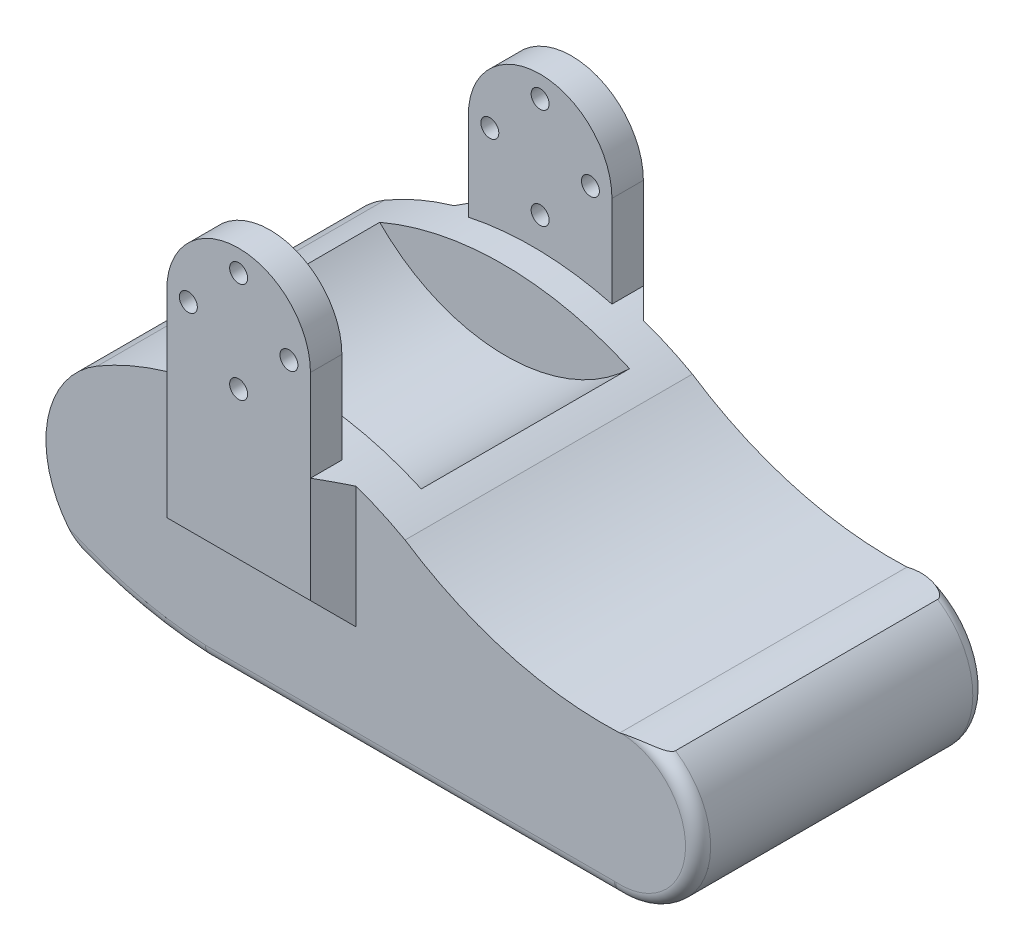
SolidWorks part; units mm, degrees
material "PLA"
ref_plane "Front Plane" through (0, 0, 0) normal (0, 0, 1) x (1, 0, 0)
ref_plane "Top Plane" through (0, 0, 0) normal (0, 1, 0) x (1, 0, 0)
ref_plane "Right Plane" through (0, 0, 0) normal (1, 0, 0) x (0, 0, -1)
sketch "Sketch1" plane through (0, 0, 0) normal (0, 0, 1) x (1, 0, 0)
  line L0 (-30, 0) -> (50, 0)
  line L1 (0, 0) -> (0, 25) construction
  line L2 (-30, 0) -> (-30, 25) construction
  line L3 (50, 0) -> (34.8329, 0) construction
  line L4 (-15, -2.8863) -> (48.734, -2.8863) construction
  line L5 (48.734, -2.8863) -> (48.734, 17.1137) construction
  line L6 (-15, -2.8863) -> (42.0254, -2.8863)
  line L7 (48.734, 17.1137) -> (42.7081, 17.1137) construction
  line L8 (-37.1668, 12.5) -> (-7.1668, 12.5) construction
  line L9 (-7.1668, 12.5) -> (12.8332, 12.5) construction
  line L10 (12.8332, 12.5) -> (12.8332, 25.4411) construction
  arc A0 (-30, 25) -> (-30, 0) centre (-22.6825, 12.5) ccw
  arc A7 (-30, 0) -> (-15, -2.8863) centre (-12.2067, 52.0503) ccw
  arc A8 (42.0254, -2.8863) -> (48.734, 17.1137) centre (42.7081, 8.0098) ccw
  arc A9 (48.734, 17.1137) -> (42.7081, 17.1137) centre (45.721, 5.4648) ccw
  arc A11 (-30, 25) -> (12.8332, 25.4411) centre (-8.1976, -12.2437) cw
  arc A12 (12.8332, 25.4411) -> (42.7081, 17.1137) centre (40.6286, 67.4056) ccw
  dimension "D5" = 20
  dimension "D6" = 30
  dimension "D1" = 30
  dimension "D2" = 50
  dimension "D3" = 25
  dimension "D4" = 25
  dimension "D7" = 20
extrude "Boss-Extrude1" add sketch "Sketch1" along normal blind 40 contours A9 A0 A7 L6 A8 region at (4.7955, 11.4421, 0)
sketch "Sketch3" plane through (0, 0, 40) normal (0, 0, 1) x (1, 0, 0)
  line L0 (-17.1668, 42.2237) -> (-17.1668, 14.7237)
  line L1 (2.8332, 42.2237) -> (2.8332, 14.7237)
  line L2 (-17.1668, 14.7237) -> (2.8332, 14.7237)
  arc A0 (2.8332, 42.2237) -> (-17.1668, 42.2237) centre (-7.1668, 42.2237) ccw
  dimension "D1" = 27.5
  dimension "D2" = 27.5
extrude "Boss-Extrude2" add sketch "Sketch3" along normal blind 3.175 and the other way blind 1.2
chamfer "Chamfer1" distance 3.175 angle 45 3 edges at (2.8332, 22.1012, 40) (-17.1668, 22.3468, 40) (-7.1668, 14.7237, 40)
sketch "Sketch2" plane through (0, 0, 40) normal (0, 0, 1) x (1, 0, 0)
  line L0 (-7.1668, 52.2237) -> (-7.1668, 49.2237) construction
  circle A0 centre (-7.1668, 49.2237) radius 1.25
  arc A1 (-7.1668, 32.2237) -> (-7.1668, 52.2237) centre (-7.1668, 42.2237) ccw construction
  circle A2 centre (-7.1668, 42.2237) radius 10 construction
  circle A3 centre (-7.1668, 42.2237) radius 7 construction
  circle A4 centre (-0.1668, 42.2237) radius 1.25
  circle A5 centre (-14.1668, 42.2237) radius 1.25
  circle A6 centre (-7.1668, 35.2237) radius 1.25
  dimension "D1" = 2.5
  dimension "D3" = 2.5
  dimension "D4" = 2.5
  dimension "D5" = 2.5
  dimension "D2" = 3
extrude "Cut-Extrude1" cut sketch "Sketch2" against normal up to next and the other way up to next
ref_plane "Plane1" through (0, 0, 20) normal (0, 0, -1) x (-1, 0, 0)
mirror "Mirror2" about plane through (0, 0, 20) normal (0, 0, -1) of "Cut-Extrude1", "Boss-Extrude2"
chamfer "Chamfer2" distance 3.175 angle 45 3 edges at (-17.1668, 22.3468, 0) (-7.1668, 14.7237, 0) (2.8332, 22.1012, 0)
ref_plane "Plane2" through (0, 0, 34.4) normal (0, 0, 1) x (1, 0, 0)
sketch "Sketch4" plane through (0, 0, 34.4) normal (0, 0, 1) x (1, 0, 0)
  arc A0 (-25.2984, 27.3795) -> (9.4872, 27.1223) centre (-7.777, 44.6437) ccw
  arc A1 (-20.3418, 29.1683) -> (-30, 25) centre (-8.1976, -12.2437) ccw construction
  arc A2 (12.8332, 25.4411) -> (6.0082, 28.5072) centre (-8.1976, -12.2437) ccw construction
  arc A3 (-25.2984, 27.3795) -> (9.4872, 27.1223) centre (-8.1976, -12.2437) cw
extrude "Cut-Extrude2" cut sketch "Sketch4" against normal blind 29
sketch "Sketch5" plane through (0, -2.8863, 0) normal (0, -1, 0) x (1, 0, 0)
  line L8 (-12, 3) -> (39.0254, 3)
  line L9 (39.0254, 3) -> (39.0254, 37)
  line L10 (39.0254, 37) -> (-12, 37)
  line L11 (-12, 37) -> (-12, 3)
  line L12 (-12, 3) -> (39.0254, 3)
  line L13 (39.0254, 3) -> (39.0254, 37)
  line L14 (39.0254, 37) -> (-12, 37)
  line L15 (-12, 37) -> (-12, 3)
  dimension "D1" = 3
extrude "Cut-Extrude3" cut sketch "Sketch5" against normal blind 3.175
fillet "Fillet6" radius 1.75 13 edges at (53.0588, 4.5379, 40) (53.0588, 4.5379, 0) (-30, 0, 20) (-22.6007, -1.9664, 40) (-22.6007, -1.9664, 0) (-15, -2.8863, 20) (13.5127, -2.8863, 40) (42.0254, -2.8863, 20) (13.5127, -2.8863, 0) (39.0254, -2.8863, 20) (13.5127, -2.8863, 37) (-12, -2.8863, 20) (13.5127, -2.8863, 3)
